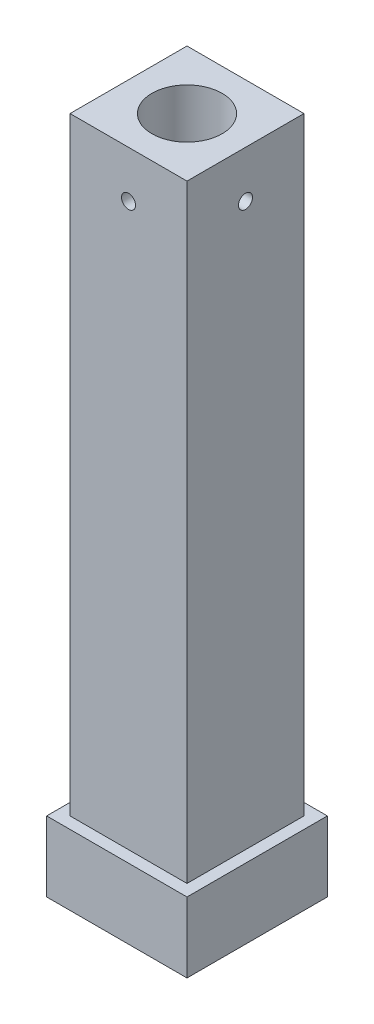
SolidWorks part; units mm, degrees
ref_plane "前视基准面" through (0, 0, 0) normal (0, 0, 1) x (1, 0, 0)
ref_plane "上视基准面" through (0, 0, 0) normal (0, 1, 0) x (1, 0, 0)
ref_plane "右视基准面" through (0, 0, 0) normal (1, 0, 0) x (0, 0, -1)
other "Configuration Table"
sketch "草图1" plane through (0, 0, 0) normal (0, 1, 0) x (1, 0, 0)
  line L1 (2.8868, 0) -> (1.4434, 2.5)
  line L2 (1.4434, 2.5) -> (-1.4434, 2.5)
  line L3 (-1.4434, 2.5) -> (-2.8868, 0)
  line L4 (-2.8868, 0) -> (-1.4434, -2.5)
  line L5 (-1.4434, -2.5) -> (1.4434, -2.5)
  line L6 (1.4434, -2.5) -> (2.8868, 0)
  line L7 (-2.5, -2.5) -> (2.5, -2.5)
  line L8 (-2.5, -2.5) -> (-2.5, 2.5)
  line L9 (-2.5, 2.5) -> (2.5, 2.5)
  line L10 (2.5, -2.5) -> (2.5, 2.5)
  line L11 (-2.5, -2.5) -> (2.5, 2.5) construction
  line L12 (-2.5, 2.5) -> (2.5, -2.5) construction
  line L13 (-3, -3) -> (3, -3)
  line L14 (-3, -3) -> (-3, 3)
  line L15 (-3, 3) -> (3, 3)
  line L16 (3, -3) -> (3, 3)
  line L17 (-3, -3) -> (3, 3) construction
  line L18 (-3, 3) -> (3, -3) construction
  circle A0 centre (0, 0) radius 2.5 construction
  circle A1 centre (0, 0) radius 1.5
  dimension "D1" = 5
  dimension "D3" = 3
  dimension "D2" = 5
  dimension "D4" = 6
extrude "凸台-拉伸1" add sketch "草图1" along normal blind 29 contours L9 L10 L7 L8
extrude "凸台-拉伸2" add sketch "草图1<5>" along normal blind 3 contours L15 L16 L13 L14
sketch "草图1<5>" plane through (0, 0, 0) normal (0, 1, 0) x (1, 0, 0) same geometry as "草图1"
extrude "切除-拉伸1" cut sketch "草图1<3>" along normal through all contours A1 region at (0, 0, 0)
sketch "草图1<3>" plane through (0, 0, 0) normal (0, 1, 0) x (1, 0, 0) same geometry as "草图1"
extrude "切除-拉伸2" cut sketch "草图1<4>" along normal blind 2 contours L1 L2 L3 L4 L5 L6
sketch "草图1<4>" plane through (0, 0, 0) normal (0, 1, 0) x (1, 0, 0) same geometry as "草图1"
sketch "草图3" plane through (0, 0, 2.5) normal (0, 0, 1) x (1, 0, 0)
  line L0 (-2.5, 29) -> (2.5, 29) construction
  line L1 (-2.5, 27) -> (2.5, 27) construction
  line L2 (-2.5, 29) -> (-2.5, 3) construction
  line L3 (2.5, 29) -> (2.5, 3) construction
  circle A0 centre (0, 27) radius 0.3
  dimension "D1" = 0.6
  dimension "D2" = 2
extrude "切除-拉伸3" cut sketch "草图3" against normal through all
sketch "草图4" plane through (-2.5, 0, 0) normal (-1, 0, 0) x (0, 0, 1)
  line L0 (-2.5, 27) -> (2.5, 27) construction
  line L1 (-2.5, 29) -> (-2.5, 3) construction
  line L2 (2.5, 29) -> (2.5, 3) construction
  line L3 (2.5, 29) -> (-2.5, 29) construction
  circle A0 centre (0, 27) radius 0.3
  dimension "D1" = 0.6
  dimension "D2" = 2
extrude "切除-拉伸4" cut sketch "草图4" against normal through all
